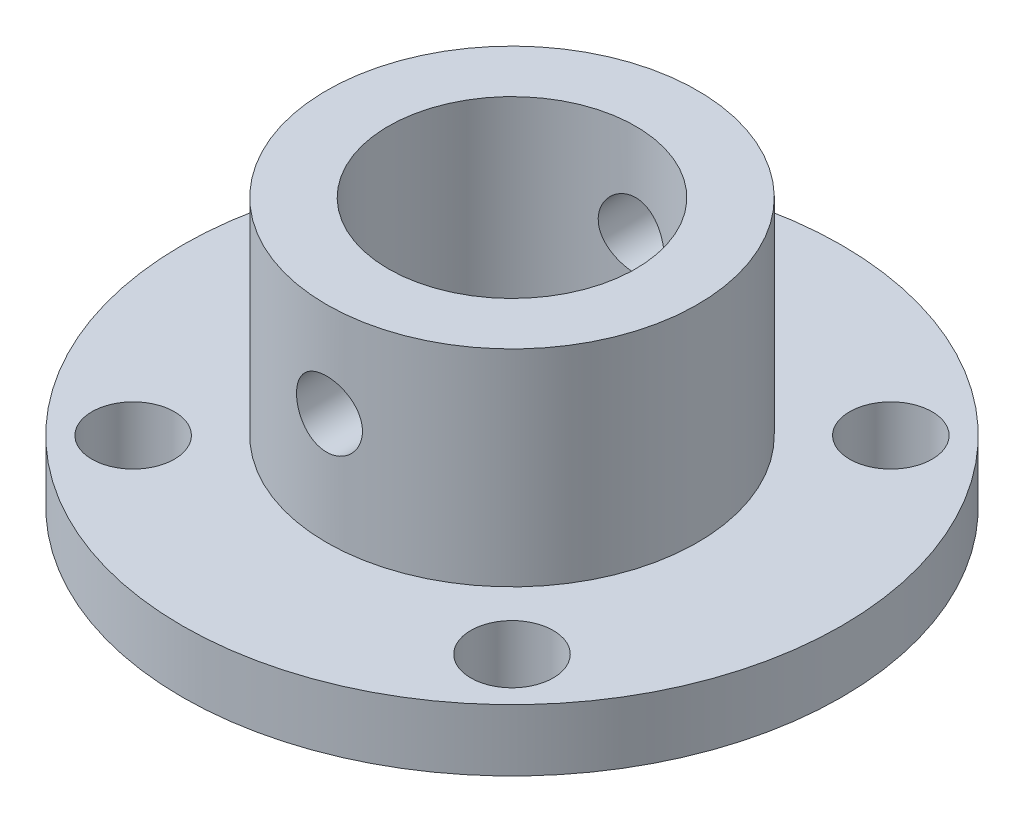
SolidWorks part; units mm, degrees
ref_plane "Front Plane" through (0, 0, 0) normal (0, 0, 1) x (1, 0, 0)
ref_plane "Top Plane" through (0, 0, 0) normal (0, 1, 0) x (1, 0, 0)
ref_plane "Right Plane" through (0, 0, 0) normal (1, 0, 0) x (0, 0, -1)
sketch "Sketch2" plane through (0, 0, 0) normal (0, 1, 0) x (1, 0, 0)
  circle A0 centre (0, 0) radius 16
  dimension "D1" = 32
extrude "Boss-Extrude1" add sketch "Sketch2" along normal blind 3
sketch "Sketch3" plane through (0, 3, 0) normal (0, 1, 0) x (1, 0, 0)
  line L0 (0, 16) -> (0, -16) construction
  line L1 (-11.3137, 11.3137) -> (11.3137, -11.3137) construction
  circle A1 centre (0, 0) radius 6
  circle A4 centre (0, 0) radius 16 construction
  circle A9 centre (-9.1924, 9.1924) radius 2
  circle A10 centre (9.1924, 9.1924) radius 2
  circle A11 centre (9.1924, -9.1924) radius 2
  circle A12 centre (-9.1924, -9.1924) radius 2
  point P12 (0, 0)
  point P20 (0, 0)
  point P23 (0, 0)
  dimension "D1" = 3
  dimension "D3" = 45
  dimension "D2" = 4
extrude "Cut-Extrude1" cut sketch "Sketch3" against normal blind 3 contours L0 A1 | A1 L0 | A11 | L0 A9 | L0 A10 | A9 L0 | A10 L0 | A12 region at (0, 3, 0) region at (-9.1924, 3, -9.1924) region at (9.1924, 3, -9.1924) region at (9.1924, 3, 9.1924) region at (-9.1924, 3, 9.1924)
sketch "Sketch4" plane through (0, 3, 0) normal (0, 1, 0) x (1, 0, 0)
  circle A0 centre (0, 0) radius 9
  circle A1 centre (0, 0) radius 6
  circle M6 centre (0, 0) radius 6
extrude "Boss-Extrude2" add sketch "Sketch4" along normal blind 10 contours A0 M6 region at (-8.7454, 3, 0)
sketch "Sketch5" plane through (0, 0, 0) normal (0, 0, 1) x (1, 0, 0)
  line L0 (0, 13) -> (0, 0) construction
  line L1 (9, 13) -> (-9, 13) construction
  line L2 (6, 13) -> (-6, 13) construction
  circle A0 centre (0, 8.4) radius 1.6
  dimension "D1" = 4.6
extrude "Cut-Extrude2" cut sketch "Sketch5" against normal mid plane 20
sketch "Sketch6" plane through (0, 0, 0) normal (0, -1, 0) x (1, 0, 0)
  line L0 (-9.1924, 9.1924) -> (9.1924, -9.1924)
  line L1 (-9.1924, 9.1924) -> (9.1924, 9.1924)
